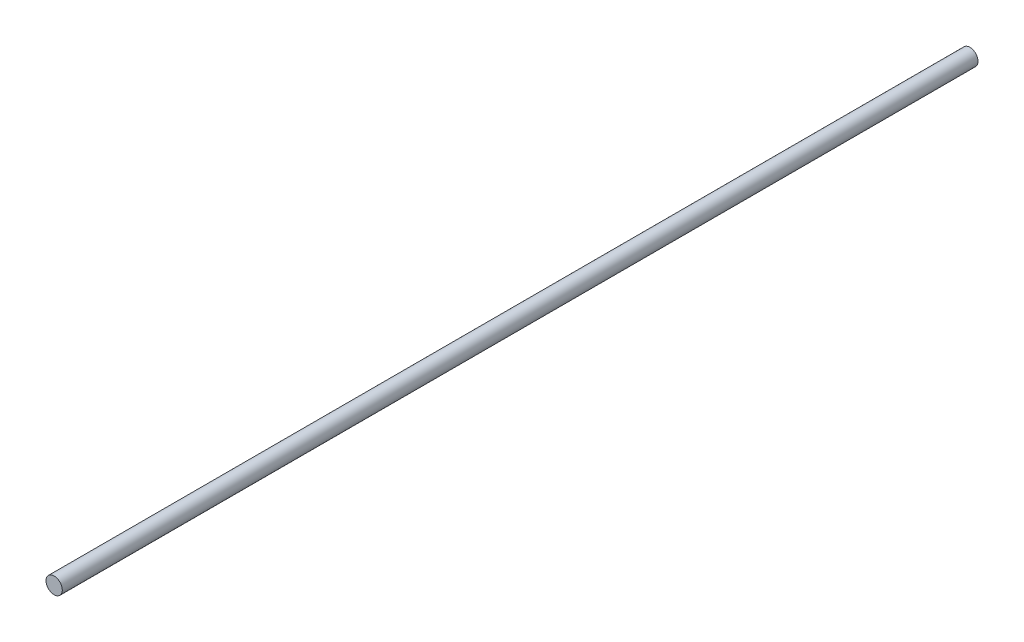
SolidWorks part; units mm, degrees
ref_plane "Front Plane" through (0, 0, 0) normal (0, 0, 1) x (1, 0, 0)
ref_plane "Top Plane" through (0, 0, 0) normal (0, 1, 0) x (1, 0, 0)
ref_plane "Right Plane" through (0, 0, 0) normal (1, 0, 0) x (0, 0, -1)
sketch "Sketch1" plane through (0, 0, 0) normal (0, 0, 1) x (1, 0, 0)
  circle A0 centre (-6.9243, 1.802) radius 4
extrude "Boss-Extrude1" add sketch "Sketch1" along normal blind 450 contours A0
